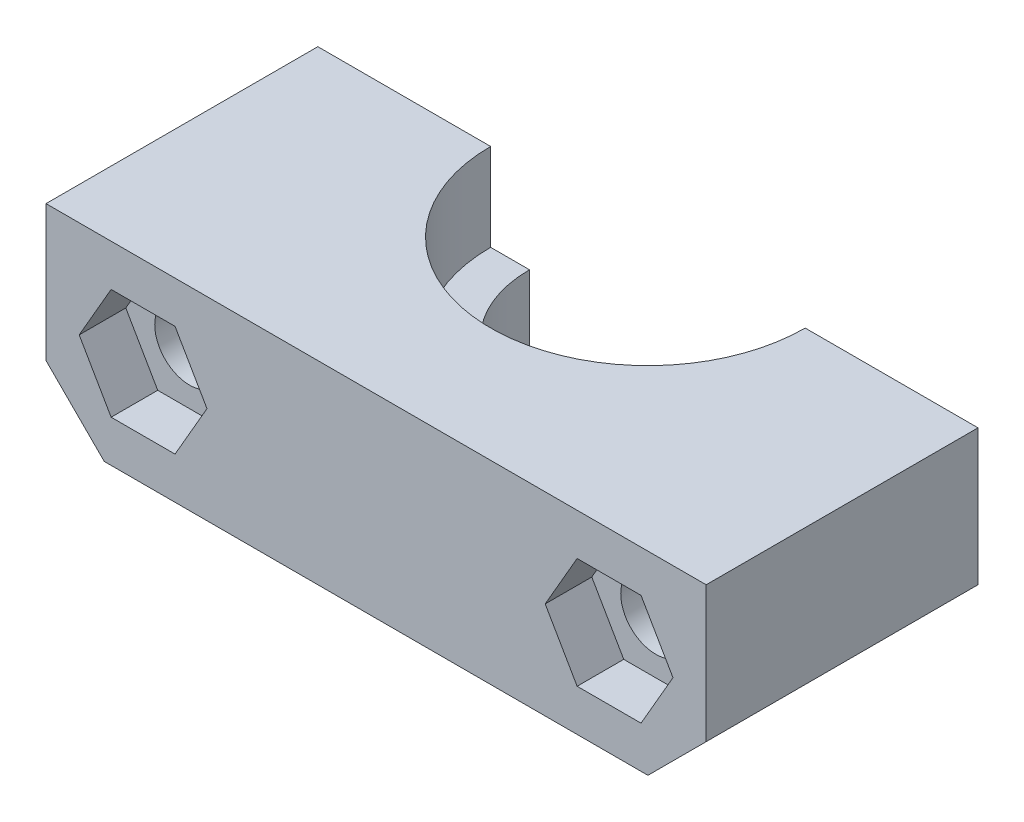
SolidWorks part; units mm, degrees
ref_plane "Front Plane" through (0, 0, 0) normal (0, 0, 1) x (1, 0, 0)
ref_plane "Top Plane" through (0, 0, 0) normal (0, 1, 0) x (1, 0, 0)
ref_plane "Right Plane" through (0, 0, 0) normal (1, 0, 0) x (0, 0, -1)
sketch "Sketch1" plane through (0, 0, 0) normal (0, 1, 0) x (1, 0, 0)
  line L1 (0, 0) -> (34, 0)
  line L2 (0, 0) -> (0, 14)
  line L3 (0, 14) -> (34, 14)
  line L4 (34, 0) -> (34, 14)
  dimension "D1" = 34
  dimension "D2" = 14
extrude "Boss-Extrude1" add sketch "Sketch1" along normal blind 10
sketch "Sketch2" plane through (0, 10, 0) normal (0, 1, 0) x (1, 0, 0)
  line L0 (34, 14) -> (0, 14) construction
  circle A0 centre (17, 14) radius 8.1
  dimension "D1" = 16.2
extrude "Cut-Extrude1" cut sketch "Sketch2" against normal blind 4.5 contours A0
sketch "Sketch4" plane through (0, 10, 0) normal (0, 1, 0) x (1, 0, 0)
  line L0 (25.1, 14) -> (8.9, 14) construction
  circle A0 centre (17, 14) radius 6.1
  dimension "D1" = 12.2
extrude "Cut-Extrude2" cut sketch "Sketch4" against normal through all both and the other way through all
sketch "Sketch5" plane through (0, 0, -14) normal (0, 0, -1) x (-1, 0, 0)
  line L0 (-29, 5) -> (-34, 5) construction
  line L3 (-34, 10) -> (-34, 0) construction
  line L4 (0, 5) -> (-5, 5) construction
  line L5 (0, 10) -> (0, 0) construction
  circle A0 centre (-29, 5) radius 1.8
  circle A1 centre (-5, 5) radius 1.8
  dimension "D1" = 3.6
  dimension "D2" = 5
extrude "Cut-Extrude3" cut sketch "Sketch5" against normal through all both and the other way through all
sketch "Sketch6" plane through (0, 0, 0) normal (0, 0, 1) x (1, 0, 0)
  line L0 (1.7091, 5) -> (6.6454, 7.85) construction
  line L1 (8.2909, 5) -> (6.6454, 7.85)
  line L2 (6.6454, 7.85) -> (3.3546, 7.85)
  line L3 (3.3546, 7.85) -> (1.7091, 5)
  line L4 (1.7091, 5) -> (3.3546, 2.15)
  line L5 (3.3546, 2.15) -> (6.6454, 2.15)
  line L6 (6.6454, 2.15) -> (8.2909, 5)
  line L7 (25.7091, 5) -> (27.3546, 2.15)
  line L8 (27.3546, 2.15) -> (30.6454, 2.15)
  line L9 (30.6454, 2.15) -> (32.2909, 5)
  line L10 (32.2909, 5) -> (30.6454, 7.85)
  line L11 (30.6454, 7.85) -> (27.3546, 7.85)
  line L12 (27.3546, 7.85) -> (25.7091, 5)
  line L13 (25.7091, 5) -> (30.6454, 7.85) construction
  circle A0 centre (5, 5) radius 2.85 construction
  circle A1 centre (29, 5) radius 2.85 construction
  dimension "D1" = 5.7
extrude "Cut-Extrude4" cut sketch "Sketch6" against normal blind 2.4
chamfer "Chamfer1" distance 3 angle 45 2 edges at (0, 0, -7) (34, 0, -7)
